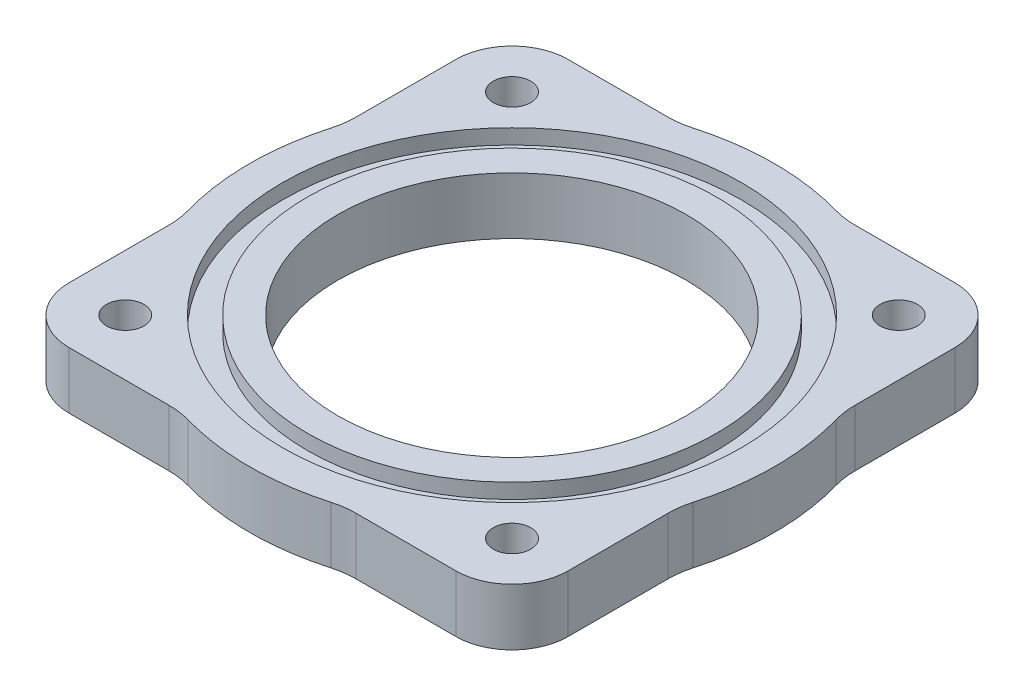
SolidWorks part; units mm, degrees
ref_plane "Front Plane" through (0, 0, 0) normal (0, 0, 1) x (1, 0, 0)
ref_plane "Top Plane" through (0, 0, 0) normal (0, 1, 0) x (1, 0, 0)
ref_plane "Right Plane" through (0, 0, 0) normal (1, 0, 0) x (0, 0, -1)
sketch "Sketch1" plane through (0, 0, 0) normal (0, 1, 0) x (1, 0, 0)
  line L0 (0, 43.6291) -> (0, 56.3563)
  line L1 (7.1437, 0) -> (19.8709, 0)
  line L2 (0, 7.1437) -> (0, 19.8709)
  line L3 (7.1437, 63.5) -> (19.8709, 63.5)
  line L4 (63.5, 7.1437) -> (63.5, 19.8709)
  line L5 (43.6291, 63.5) -> (56.3563, 63.5)
  line L6 (63.5, 43.6291) -> (63.5, 56.3563)
  line L7 (43.6291, 0) -> (56.3563, 0)
  circle A0 centre (31.75, 31.75) radius 22.1742
  circle A1 centre (56.3563, 56.3563) radius 2.3812
  circle A2 centre (56.3563, 7.1437) radius 2.3812
  circle A3 centre (7.1437, 7.1437) radius 2.3812
  circle A4 centre (7.1437, 56.3563) radius 2.3812
  arc A7 (7.1437, 63.5) -> (0, 56.3563) centre (7.1437, 56.3563) ccw
  arc A8 (56.3563, 0) -> (63.5, 7.1437) centre (56.3563, 7.1437) ccw
  arc A9 (0, 7.1437) -> (7.1437, 0) centre (7.1437, 7.1437) ccw
  arc A10 (63.5, 56.3563) -> (56.3563, 63.5) centre (56.3563, 56.3563) ccw
  arc A11 (-0.3851, 40.8585) -> (-0.3851, 22.6415) centre (31.75, 31.75) ccw
  arc A12 (22.6415, -0.3851) -> (40.8585, -0.3851) centre (31.75, 31.75) ccw
  arc A13 (40.8585, 63.8851) -> (22.6415, 63.8851) centre (31.75, 31.75) ccw
  arc A14 (63.8851, 22.6415) -> (63.8851, 40.8585) centre (31.75, 31.75) ccw
  arc A15 (63.8851, 40.8585) -> (63.5, 43.6291) centre (73.66, 43.6291) cw
  arc A16 (63.5, 19.8709) -> (63.8851, 22.6415) centre (73.66, 19.8709) cw
  arc A17 (40.8585, -0.3851) -> (43.6291, 0) centre (43.6291, -10.16) cw
  arc A18 (22.6415, -0.3851) -> (19.8709, 0) centre (19.8709, -10.16) ccw
  arc A19 (0, 19.8709) -> (-0.3851, 22.6415) centre (-10.16, 19.8709) ccw
  arc A20 (-0.3851, 40.8585) -> (0, 43.6291) centre (-10.16, 43.6291) ccw
  arc A21 (22.6415, 63.8851) -> (19.8709, 63.5) centre (19.8709, 73.66) cw
  arc A22 (43.6291, 63.5) -> (40.8585, 63.8851) centre (43.6291, 73.66) cw
  point P16 (63.5, 42.1213)
  point P31 (63.5, 21.3787)
  point P34 (42.1213, 0)
  point P41 (0, 42.1213)
  point P46 (42.1213, 63.5)
  dimension "D3" = 44.3484
  dimension "D6" = 4.7625
  dimension "D7" = 4.7625
  dimension "D8" = 4.7625
  dimension "D9" = 4.7625
  dimension "D10" = 7.1437
  dimension "D11" = 7.1437
  dimension "D12" = 7.1437
  dimension "D13" = 7.1437
  dimension "D14" = 7.1437
  dimension "D15" = 7.1437
  dimension "D16" = 7.1437
  dimension "D17" = 7.1437
  dimension "D18" = 49.2125
  dimension "D2" = 10.16
  dimension "D19" = 11.2268
  dimension "D4" = 31.75
  dimension "D5" = 31.75
extrude "Boss-Extrude1" add sketch "Sketch1" against normal blind 7.239
sketch "Sketch2" plane through (0, 0, 0) normal (0, 1, 0) x (1, 0, 0)
  circle A0 centre (31.75, 31.75) radius 26.035
  circle A1 centre (31.75, 31.75) radius 29.21
  dimension "D1" = 52.07
  dimension "D2" = 58.42
extrude "Cut-Extrude1" cut sketch "Sketch2" against normal blind 1.905
